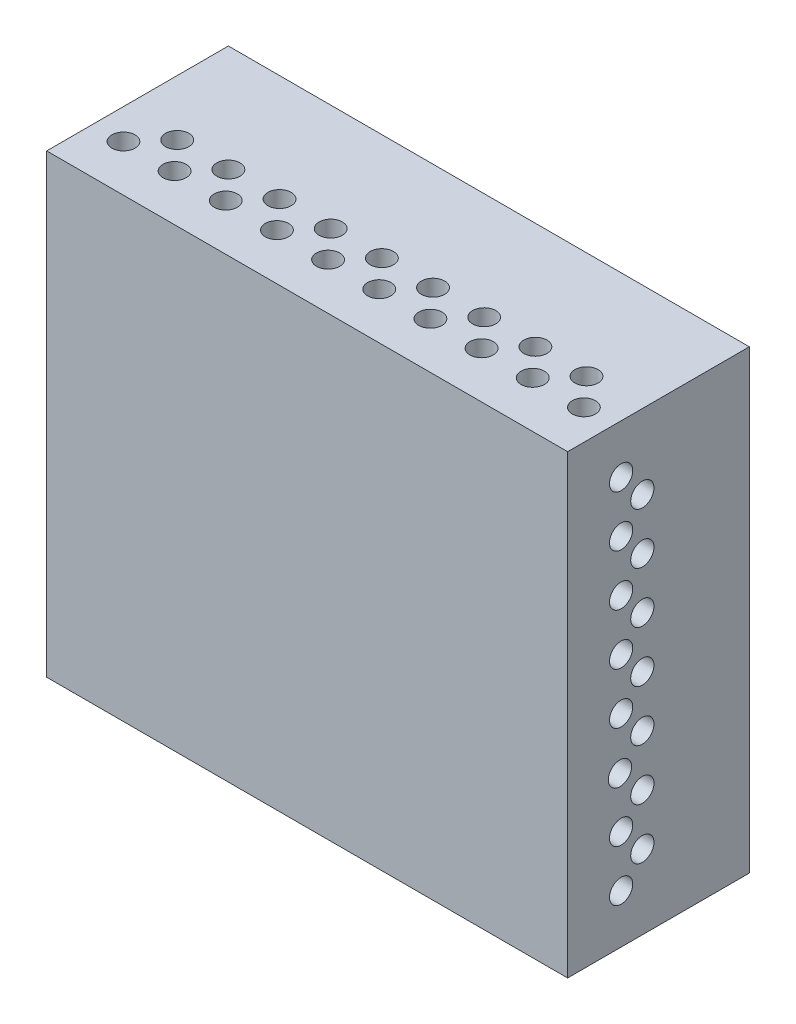
SolidWorks part; units mm, degrees
ref_plane "Piano frontale" through (0, 0, 0) normal (0, 0, 1) x (1, 0, 0)
ref_plane "Piano superiore" through (0, 0, 0) normal (0, 1, 0) x (1, 0, 0)
ref_plane "Piano destro" through (0, 0, 0) normal (1, 0, 0) x (0, 0, -1)
sketch "Schizzo1" plane through (0, 0, 0) normal (0, 0, 1) x (1, 0, 0)
  line L1 (0, 0) -> (56, 0)
  line L2 (0, 0) -> (0, 49)
  line L3 (0, 49) -> (56, 49)
  line L4 (56, 0) -> (56, 49)
  dimension "D1" = 49
  dimension "D2" = 56
extrude "Estrusione-Estrusione1" add sketch "Schizzo1" along normal blind 2
sketch "Schizzo2" plane through (0, 0, 0) normal (0, 0, -1) x (-1, 0, 0)
  line L0 (-56, 49) -> (0, 49) construction
  line L1 (-56, 0) -> (-54, 0)
  line L2 (-56, 0) -> (-56, 49)
  line L3 (-56, 49) -> (-54, 49)
  line L4 (-54, 0) -> (-54, 49)
  dimension "D1" = 2
extrude "Estrusione-Estrusione2" add sketch "Schizzo2" along normal blind 8.53
sketch "Schizzo3" plane through (0, 0, 0) normal (0, 0, -1) x (-1, 0, 0)
  line L0 (0, 49) -> (0, 0) construction
  line L1 (-54, 0) -> (0, 0)
  line L2 (-54, 0) -> (-54, 2)
  line L3 (-54, 2) -> (0, 2)
  line L4 (0, 0) -> (0, 2)
  dimension "D1" = 2
extrude "Estrusione-Estrusione3" add sketch "Schizzo3" along normal blind 8.53
sketch "Schizzo4" plane through (0, 0, 0) normal (0, 0, -1) x (-1, 0, 0)
  line L0 (-54, 49) -> (0, 49) construction
  line L1 (0, 2) -> (-2, 2)
  line L2 (0, 2) -> (0, 49)
  line L3 (0, 49) -> (-2, 49)
  line L4 (-2, 2) -> (-2, 49)
  dimension "D1" = 2
extrude "Estrusione-Estrusione4" add sketch "Schizzo4" along normal blind 8.53
sketch "Schizzo5" plane through (0, 0, 0) normal (0, 0, -1) x (-1, 0, 0)
  line L0 (-2, 49) -> (-2, 2) construction
  line L1 (-54, 49) -> (-2, 49)
  line L2 (-54, 49) -> (-54, 47)
  line L3 (-54, 47) -> (-2, 47)
  line L4 (-2, 49) -> (-2, 47)
  dimension "D1" = 2
extrude "Estrusione-Estrusione5" add sketch "Schizzo5" along normal blind 8.53
sketch "Schizzo6" plane through (0, 0, 0) normal (0, 0, -1) x (-1, 0, 0)
  line L1 (-2, 2) -> (-54, 2) construction
  line L3 (-48.5, 2) -> (-50.5, 2)
  line L4 (-48.5, 2) -> (-48.5, 43)
  line L5 (-48.5, 43) -> (-50.5, 43)
  line L6 (-50.5, 2) -> (-50.5, 43)
  dimension "D2" = 2
  dimension "D3" = 41
extrude "Estrusione-Estrusione6" add sketch "Schizzo6" along normal blind 7.5
sketch "Schizzo7" plane through (0, 0, 0) normal (0, -1, 0) x (1, 0, 0)
  line L1 (32.1119, -1.8307) -> (23.5303, -1.8307)
  line L2 (32.1119, -1.8307) -> (32.1119, -6.6965)
  line L3 (32.1119, -6.6965) -> (23.5303, -6.6965)
  line L4 (23.5303, -1.8307) -> (23.5303, -6.6965)
extrude "Taglio-Estrusione1" cut sketch "Schizzo7" against normal blind 2
sketch "Schizzo8" plane through (0, 0, -7.5) normal (0, 0, -1) x (-1, 0, 0)
  line L1 (-50.5, 2) -> (-48.5, 2)
  line L2 (-50.5, 2) -> (-50.5, 43)
  line L3 (-50.5, 43) -> (-48.5, 43)
  line L4 (-48.5, 2) -> (-48.5, 43)
extrude "Estrusione-Estrusione7" add sketch "Schizzo8" along normal blind 0.88
sketch "Schizzo9" plane through (0, 0, 0) normal (0, 0, -1) x (-1, 0, 0)
  line L1 (-50.5, 43) -> (-7.5, 43)
  line L2 (-50.5, 43) -> (-50.5, 45)
  line L3 (-50.5, 45) -> (-7.5, 45)
  line L4 (-7.5, 43) -> (-7.5, 45)
  dimension "D1" = 43
  dimension "D2" = 2
extrude "Estrusione-Estrusione8" add sketch "Schizzo9" along normal blind 8.38
sketch "Schizzo10" plane through (0, 0, 0) normal (0, 0, -1) x (-1, 0, 0)
  line L0 (-2, 2) -> (-48.5, 2) construction
  line L1 (-7.5, 45) -> (-5.5, 45)
  line L2 (-7.5, 45) -> (-7.5, 2)
  line L3 (-7.5, 2) -> (-5.5, 2)
  line L4 (-5.5, 45) -> (-5.5, 2)
  dimension "D1" = 2
extrude "Estrusione-Estrusione9" add sketch "Schizzo10" along normal blind 8.38
sketch "Schizzo11" plane through (5.5, 0, 0) normal (-1, 0, 0) x (0, 0, 1)
  line L1 (0, 2) -> (0, 45) construction
  line L5 (0, 5) -> (-7.4, 5)
  line L6 (0, 5) -> (0, 40)
  line L7 (0, 40) -> (-7.4, 40)
  line L8 (-7.4, 5) -> (-7.4, 40)
  point P10 (0, 3.5)
  dimension "D1" = 7.4
extrude "Taglio-Estrusione2" cut sketch "Schizzo11" against normal blind 2
sketch "Schizzo12" plane through (50.5, 0, 0) normal (1, 0, 0) x (0, 0, -1)
  line L1 (0, 45) -> (0, 2) construction
  line L4 (0, 40) -> (7.4, 40)
  line L5 (0, 40) -> (0, 5)
  line L6 (0, 5) -> (7.4, 5)
  line L7 (7.4, 40) -> (7.4, 5)
  dimension "D3" = 7.4
extrude "Taglio-Estrusione3" cut sketch "Schizzo12" against normal blind 2
sketch "Schizzo14" plane through (0, 0, -8.38) normal (0, 0, -1) x (-1, 0, 0)
  line L0 (-48.5, 2) -> (-48.5, 43) construction
  line L1 (-48.5, 18.8) -> (-50.5, 18.8)
  line L2 (-48.5, 18.8) -> (-48.5, 32.9078)
  line L3 (-48.5, 32.9078) -> (-50.5, 32.9078)
  line L4 (-50.5, 18.8) -> (-50.5, 32.9078)
  line L5 (-48.5, 18.8) -> (-47.1, 20.7) construction
  line L6 (-50.5, 45) -> (-50.5, 2) construction
extrude "Taglio-Estrusione5" cut sketch "Schizzo14" against normal blind 2
sketch "Schizzo15" plane through (0, 0, -7.4) normal (0, 0, 1) x (1, 0, 0)
  line L0 (50.5, 5) -> (50.5, 18.8) construction
  line L1 (48.5, 18.8) -> (50.5, 18.8)
  line L2 (48.5, 18.8) -> (48.5, 16.8)
  line L3 (48.5, 16.8) -> (50.5, 16.8)
  line L4 (50.5, 18.8) -> (50.5, 16.8)
  dimension "D1" = 2
extrude "Estrusione-Estrusione10" add sketch "Schizzo15" along normal blind 7.5
sketch "Schizzo16" plane through (0, 0, 0) normal (0, 0, -1) x (-1, 0, 0)
  line L1 (-48.5, 2) -> (-44.03, 2)
  line L2 (-48.5, 2) -> (-48.5, 6)
  line L3 (-48.5, 6) -> (-44.03, 6)
  line L4 (-44.03, 2) -> (-44.03, 6)
  dimension "D1" = 4
  dimension "D2" = 4.47
extrude "Estrusione-Estrusione11" add sketch "Schizzo16" along normal blind 6.78
sketch "Schizzo17" plane through (0, 0, 0) normal (0, 0, -1) x (-1, 0, 0)
  line L1 (-7.5, 43) -> (-12.5, 43)
  line L2 (-7.5, 43) -> (-7.5, 38)
  line L3 (-7.5, 38) -> (-12.5, 38)
  line L4 (-12.5, 43) -> (-12.5, 38)
  dimension "D1" = 5
  dimension "D2" = 5
extrude "Estrusione-Estrusione12" add sketch "Schizzo17" along normal blind 6.78
sketch "Schizzo18" plane through (0, 0, 0) normal (0, 0, -1) x (-1, 0, 0)
  line L1 (-7.5, 2) -> (-12.5, 2)
  line L2 (-7.5, 2) -> (-7.5, 7)
  line L3 (-7.5, 7) -> (-12.5, 7)
  line L4 (-12.5, 2) -> (-12.5, 7)
  dimension "D1" = 5
  dimension "D2" = 5
extrude "Estrusione-Estrusione13" add sketch "Schizzo18" along normal blind 6.78
sketch "Schizzo19" plane through (0, 0, 0) normal (0, 0, -1) x (-1, 0, 0)
  line L1 (-48.5, 43) -> (-43.5, 43)
  line L2 (-48.5, 43) -> (-48.5, 38)
  line L3 (-48.5, 38) -> (-43.5, 38)
  line L4 (-43.5, 43) -> (-43.5, 38)
  dimension "D1" = 5
  dimension "D2" = 5
extrude "Estrusione-Estrusione14" add sketch "Schizzo19" along normal blind 6.78
sketch "Schizzo20" plane through (0, 43, 0) normal (0, -1, 0) x (1, 0, 0)
  line L0 (12.5, -6.78) -> (12.5, 0) construction
  line L1 (43.5, 0) -> (12.5, 0)
  line L2 (43.5, 0) -> (43.5, -7.4)
  line L3 (43.5, -7.4) -> (12.5, -7.4)
  line L4 (12.5, 0) -> (12.5, -7.4)
  dimension "D1" = 7.4
extrude "Taglio-Estrusione6" cut sketch "Schizzo20" against normal blind 2
sketch "Schizzo21" plane through (0, 0, 0) normal (0, 0, -1) x (-1, 0, 0)
  line L1 (-48.5, 6) -> (-50.5, 6)
  line L2 (-48.5, 6) -> (-48.5, 5)
  line L3 (-48.5, 5) -> (-50.5, 5)
  line L4 (-50.5, 6) -> (-50.5, 5)
extrude "Estrusione-Estrusione15" add sketch "Schizzo21" along normal blind 7.4
sketch "Schizzo22" plane through (0, 0, 0) normal (0, 0, -1) x (-1, 0, 0)
  line L1 (-5.5, 5) -> (-7.5, 5)
  line L2 (-5.5, 5) -> (-5.5, 7)
  line L3 (-5.5, 7) -> (-7.5, 7)
  line L4 (-7.5, 5) -> (-7.5, 7)
extrude "Estrusione-Estrusione16" add sketch "Schizzo22" along normal blind 7.4
sketch "Schizzo23" plane through (0, 0, 0) normal (0, 0, -1) x (-1, 0, 0)
  line L1 (-5.5, 40) -> (-7.5, 40)
  line L2 (-5.5, 40) -> (-5.5, 38)
  line L3 (-5.5, 38) -> (-7.5, 38)
  line L4 (-7.5, 40) -> (-7.5, 38)
extrude "Estrusione-Estrusione17" add sketch "Schizzo23" along normal blind 7.4
sketch "Schizzo24" plane through (0, 0, 0) normal (0, 0, -1) x (-1, 0, 0)
  line L1 (-48.5, 38) -> (-50.5, 38)
  line L2 (-48.5, 38) -> (-48.5, 40)
  line L3 (-48.5, 40) -> (-50.5, 40)
  line L4 (-50.5, 38) -> (-50.5, 40)
extrude "Estrusione-Estrusione18" add sketch "Schizzo24" along normal blind 7.4
sketch "Schizzo25" plane through (0, 0, -6.78) normal (0, 0, -1) x (-1, 0, 0)
  circle A0 centre (-46.2, 4.2) radius 1
  circle A1 centre (-10, 40.5) radius 1
  dimension "D1" = 2
  dimension "D2" = 2
extrude "Taglio-Estrusione7" cut sketch "Schizzo25" against normal blind 4
sketch "Schizzo26" plane through (0, 0, -8.53) normal (0, 0, -1) x (-1, 0, 0)
  line L0 (0, 0) -> (0, 49) construction
  line L1 (-56, 0) -> (0, 0)
  line L2 (-56, 0) -> (-56, 1)
  line L3 (-56, 1) -> (0, 1)
  line L4 (0, 0) -> (0, 1)
  dimension "D1" = 1
extrude "Estrusione-Estrusione19" add sketch "Schizzo26" along normal blind 9
sketch "Schizzo27" plane through (0, 0, -8.53) normal (0, 0, -1) x (-1, 0, 0)
  line L0 (0, 49) -> (-56, 49) construction
  line L1 (0, 1) -> (-1, 1)
  line L2 (0, 1) -> (0, 49)
  line L3 (0, 49) -> (-1, 49)
  line L4 (-1, 1) -> (-1, 49)
  dimension "D1" = 1
extrude "Estrusione-Estrusione20" add sketch "Schizzo27" along normal blind 9
sketch "Schizzo28" plane through (0, 0, -8.53) normal (0, 0, -1) x (-1, 0, 0)
  line L0 (-56, 49) -> (-56, 1) construction
  line L1 (-1, 49) -> (-56, 49)
  line L2 (-1, 49) -> (-1, 48)
  line L3 (-1, 48) -> (-56, 48)
  line L4 (-56, 49) -> (-56, 48)
  dimension "D1" = 1
extrude "Estrusione-Estrusione21" add sketch "Schizzo28" along normal blind 9
sketch "Schizzo29" plane through (0, 0, -8.53) normal (0, 0, -1) x (-1, 0, 0)
  line L0 (-56, 48) -> (-1, 48) construction
  line L1 (-56, 1) -> (-55, 1)
  line L2 (-56, 1) -> (-56, 48)
  line L3 (-56, 48) -> (-55, 48)
  line L4 (-55, 1) -> (-55, 48)
  dimension "D1" = 1
extrude "Estrusione-Estrusione22" add sketch "Schizzo29" along normal blind 9
sketch "Schizzo30" plane through (54, 0, 0) normal (-1, 0, 0) x (0, 0, 1)
  circle A0 centre (-3.75, 5.25) radius 1.25
  circle A1 centre (-3.75, 10.75) radius 1.25
  circle A2 centre (-3.6234, 16.25) radius 1.25
  circle A3 centre (-3.75, 21.75) radius 1.25
  circle A4 centre (-3.75, 27.25) radius 1.25
  circle A5 centre (-3.75, 32.75) radius 1.25
  circle A6 centre (-3.75, 38.25) radius 1.25
  circle A7 centre (-3.75, 43.75) radius 1.25
  dimension "D10" = 2.5
  dimension "D11" = 2.5
  dimension "D12" = 2.5
  dimension "D13" = 2.5
  dimension "D14" = 2.5
  dimension "D15" = 2.5
  dimension "D16" = 2.5
  dimension "D17" = 2.5
  dimension "D3" = 5.5
  dimension "D6" = 5.5
  dimension "D7" = 5.5
  dimension "D8" = 5.5
  dimension "D9" = 5.5
extrude "Taglio-Estrusione8" cut sketch "Schizzo30" against normal blind 2
sketch "Schizzo31" plane through (54, 0, 0) normal (-1, 0, 0) x (0, 0, 1)
  circle A0 centre (-6.03, 41) radius 1.25
  circle A1 centre (-6.03, 35.5) radius 1.25
  circle A2 centre (-6.03, 30) radius 1.25
  circle A3 centre (-6.03, 24.5) radius 1.25
  circle A4 centre (-6.03, 19) radius 1.25
  circle A5 centre (-6.03, 13.5) radius 1.25
  circle A6 centre (-6.03, 8) radius 1.25
  dimension "D9" = 2.5
  dimension "D10" = 2.5
  dimension "D11" = 2.5
  dimension "D12" = 2.5
  dimension "D13" = 2.5
  dimension "D14" = 2.5
  dimension "D15" = 2.5
  dimension "D3" = 5.5
  dimension "D4" = 5.5
  dimension "D5" = 5.5
  dimension "D6" = 5.5
  dimension "D7" = 5.5
  dimension "D8" = 5.5
extrude "Taglio-Estrusione9" cut sketch "Schizzo31" against normal blind 2
sketch "Schizzo32" plane through (2, 0, 0) normal (1, 0, 0) x (0, 0, -1)
  circle A0 centre (2.5, 43.75) radius 1.25
  circle A1 centre (2.5, 38.25) radius 1.25
  circle A2 centre (2.5, 32.75) radius 1.25
  circle A3 centre (2.5, 27.25) radius 1.25
  circle A4 centre (2.5, 21.75) radius 1.25
  circle A5 centre (2.5, 16.25) radius 1.25
  circle A6 centre (2.5, 10.75) radius 1.25
  circle A7 centre (2.5, 5.25) radius 1.25
  dimension "D10" = 2.5
  dimension "D11" = 2.5
  dimension "D12" = 2.5
  dimension "D13" = 2.5
  dimension "D14" = 2.5
  dimension "D15" = 2.5
  dimension "D16" = 2.5
  dimension "D17" = 2.5
  dimension "D3" = 5.5
  dimension "D4" = 5.5
  dimension "D5" = 5.5
  dimension "D7" = 5.5
  dimension "D8" = 5.5
  dimension "D9" = 5.5
extrude "Taglio-Estrusione10" cut sketch "Schizzo32" against normal blind 2
sketch "Schizzo33" plane through (2, 0, 0) normal (1, 0, 0) x (0, 0, -1)
  circle A0 centre (6.03, 8) radius 1.25
  circle A1 centre (6.03, 13.5) radius 1.25
  circle A2 centre (6.03, 41) radius 1.25
  circle A3 centre (6.03, 35.5) radius 1.25
  circle A4 centre (6.03, 30) radius 1.25
  circle A5 centre (6.03, 24.5) radius 1.25
  circle A6 centre (6.03, 19) radius 1.25
  dimension "D9" = 2.5
  dimension "D10" = 2.5
  dimension "D11" = 2.5
  dimension "D12" = 2.5
  dimension "D13" = 2.5
  dimension "D14" = 2.5
  dimension "D15" = 2.5
  dimension "D3" = 5.5
  dimension "D4" = 5.5
  dimension "D5" = 5.5
  dimension "D6" = 5.5
  dimension "D7" = 5.5
  dimension "D8" = 5.5
extrude "Taglio-Estrusione11" cut sketch "Schizzo33" against normal blind 2
sketch "Schizzo35" plane through (0, 47, 0) normal (0, -1, 0) x (-1, 0, 0)
  circle A0 centre (-3.25, 3) radius 1.245
  circle A1 centre (-8.75, 3) radius 1.25
  circle A2 centre (-14.25, 3) radius 1.25
  circle A3 centre (-19.75, 3) radius 1.25
  circle A4 centre (-25.25, 3) radius 1.25
  circle A5 centre (-30.75, 3) radius 1.25
  circle A6 centre (-36.25, 3) radius 1.25
  circle A7 centre (-41.75, 3) radius 1.25
  circle A8 centre (-47.25, 3) radius 1.25
  circle A9 centre (-52.75, 3) radius 1.245
  dimension "D12" = 2.49
  dimension "D13" = 2.5
  dimension "D14" = 2.5
  dimension "D15" = 2.5
  dimension "D16" = 2.5
  dimension "D17" = 2.5
  dimension "D18" = 2.5
  dimension "D19" = 2.5
  dimension "D20" = 2.5
  dimension "D21" = 2.49
  dimension "D3" = 5.5
  dimension "D4" = 5.5
  dimension "D5" = 5.5
  dimension "D6" = 5.5
  dimension "D7" = 5.5
  dimension "D8" = 5.5
  dimension "D9" = 5.5
  dimension "D10" = 5.5
  dimension "D11" = 5.5
extrude "Taglio-Estrusione12" cut sketch "Schizzo35" against normal blind 2
sketch "Schizzo37" plane through (0, 47, 0) normal (0, -1, 0) x (-1, 0, 0)
  circle A0 centre (-50, 6.03) radius 1.25
  circle A1 centre (-44.5, 6.03) radius 1.25
  circle A2 centre (-39, 6.03) radius 1.25
  circle A3 centre (-33.5, 6.03) radius 1.25
  circle A4 centre (-28, 6.03) radius 1.25
  circle A5 centre (-22.5, 6.03) radius 1.25
  circle A6 centre (-17, 6.03) radius 1.25
  circle A7 centre (-11.5, 6.03) radius 1.25
  circle A8 centre (-6, 6.03) radius 1.25
  dimension "D11" = 2.5
  dimension "D12" = 2.5
  dimension "D13" = 2.5
  dimension "D14" = 2.5
  dimension "D15" = 2.5
  dimension "D16" = 2.5
  dimension "D17" = 2.5
  dimension "D18" = 2.5
  dimension "D19" = 2.5
  dimension "D3" = 5.5
  dimension "D4" = 5.5
  dimension "D5" = 5.5
  dimension "D6" = 5.5
  dimension "D7" = 5.5
  dimension "D8" = 5.5
  dimension "D9" = 5.5
  dimension "D10" = 5.5
extrude "Taglio-Estrusione13" cut sketch "Schizzo37" against normal blind 2
sketch "Schizzo38" plane through (0, 2, 0) normal (0, 1, 0) x (1, 0, 0)
  circle A0 centre (52.25, 3.75) radius 1.25
  circle A1 centre (3.75, 3.75) radius 1.25
  dimension "D3" = 2.5
  dimension "D4" = 2.5
extrude "Taglio-Estrusione14" cut sketch "Schizzo38" against normal blind 2
sketch "Schizzo39" plane through (0, 2, 0) normal (0, 1, 0) x (1, 0, 0)
  circle A0 centre (41.28, 3.75) radius 1.25
  circle A1 centre (35.78, 3.75) radius 1.25
  dimension "D5" = 2.5
  dimension "D6" = 2.5
  dimension "D4" = 5.5
extrude "Taglio-Estrusione15" cut sketch "Schizzo39" against normal blind 2
sketch "Schizzo40" plane through (0, 2, 0) normal (0, 1, 0) x (1, 0, 0)
  circle A0 centre (15.25, 3.75) radius 1.25
  circle A1 centre (20.75, 3.75) radius 1.25
  dimension "D4" = 2.5
  dimension "D5" = 2.5
  dimension "D3" = 5.5
extrude "Taglio-Estrusione16" cut sketch "Schizzo40" against normal blind 2
sketch "Schizzo41" plane through (0, 2, 0) normal (0, 1, 0) x (1, 0, 0)
  circle A0 centre (38.53, 5.38) radius 1.25
  dimension "D3" = 2.5
extrude "Taglio-Estrusione17" cut sketch "Schizzo41" against normal blind 2
sketch "Schizzo42" plane through (0, 2, 0) normal (0, 1, 0) x (1, 0, 0)
  circle A0 centre (18, 5.38) radius 1.25
  dimension "D3" = 2.5
extrude "Taglio-Estrusione18" cut sketch "Schizzo42" against normal blind 2
sketch "Schizzo43" plane through (0, 0, 0) normal (0, -1, 0) x (-1, 0, 0)
  text T0 "I"
  point P1 (-31.2395, 8.69)
  point P2 (-31.1878, 7.3577)
  point P3 (-31.0329, 8.1553)
extrude "Estrusione-Estrusione23" add sketch "Schizzo43" along normal blind 1
sketch "Schizzo44" plane through (0, 0, 0) normal (0, -1, 0) x (-1, 0, 0)
  text T0 "0"
extrude "Estrusione-Estrusione24" add sketch "Schizzo44" along normal blind 1
